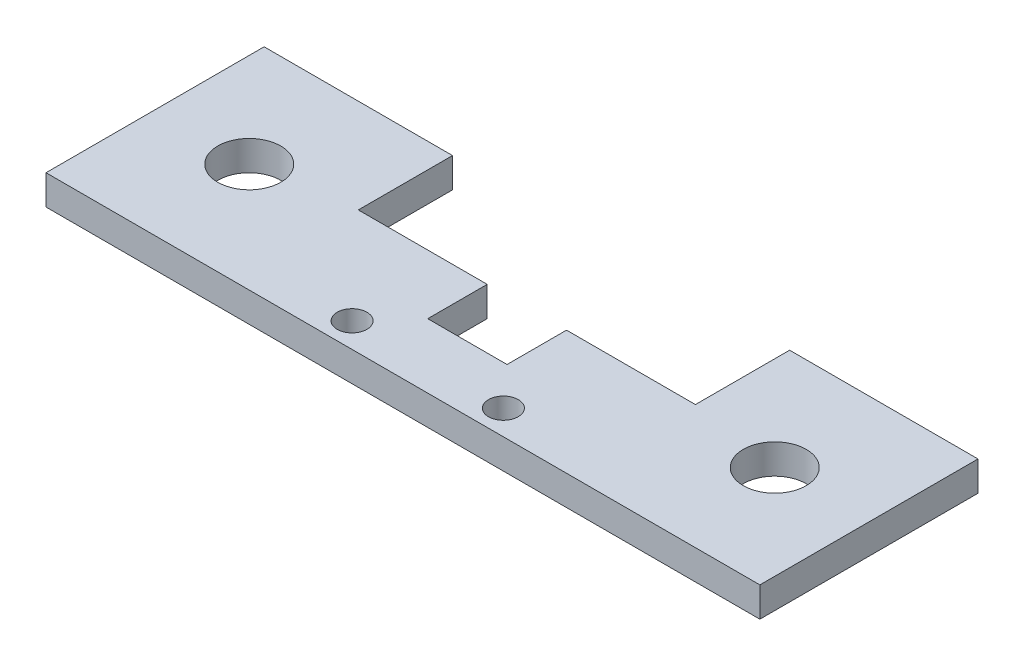
SolidWorks part; units mm, degrees
ref_plane "Front Plane" through (0, 0, 0) normal (0, 0, 1) x (1, 0, 0)
ref_plane "Top Plane" through (0, 0, 0) normal (0, 1, 0) x (1, 0, 0)
ref_plane "Right Plane" through (0, 0, 0) normal (1, 0, 0) x (0, 0, -1)
sketch "Sketch1" plane through (0, 0, 0) normal (0, 1, 0) x (1, 0, 0)
  line L0 (-4, 0) -> (-4, -5.5) construction
  line L1 (0, 0) -> (-8, 0)
  line L2 (0, 0) -> (0, -6)
  line L3 (0, -6) -> (-8, -6)
  line L4 (-8, 0) -> (-8, -6)
  line L5 (-21, 0) -> (13, 0)
  line L6 (-21, 0) -> (-21, -12.5)
  line L7 (-21, -12.5) -> (13, -12.5)
  line L8 (13, 0) -> (13, -12.5)
  line L9 (13, 9.5) -> (32, 9.5)
  line L10 (-21, -12.5) -> (13, 0) construction
  line L11 (-4, -5.5) -> (-4, -13.3) construction
  line L12 (-14.13, -13.3) -> (6.13, -13.3) construction
  line L13 (6.13, -13.3) -> (6.13, 2.3) construction
  line L14 (6.13, -13.3) -> (3.63, -13.3) construction
  line L15 (3.63, -13.3) -> (3.63, -10) construction
  line L16 (-4, -5.5) -> (6.13, -5.5) construction
  line L17 (-14.13, -13.3) -> (-14.13, 2.3) construction
  line L18 (-14.13, 2.3) -> (6.13, 2.3) construction
  line L19 (-4, -9.35) -> (-4, -17.6) construction
  line L20 (-21, -12.5) -> (-40, -12.5)
  line L21 (-21, -12.5) -> (-21, 9.5)
  line L22 (-21, 9.5) -> (-40, 9.5)
  line L23 (-40, -12.5) -> (-40, 9.5)
  line L24 (13, 0) -> (13, -12.5)
  line L25 (13, -12.5) -> (32, -12.5)
  line L26 (32, -12.5) -> (32, 9.5)
  line L27 (-30.5, -12.5) -> (-30.5, 9.5) construction
  line L28 (-40, -1.5) -> (-21, -1.5) construction
  line L29 (32, -1.5) -> (13, -1.5) construction
  line L30 (22.5, -12.5) -> (22.5, 9.5) construction
  line L31 (13, 0) -> (13, 9.5)
  circle A0 centre (3.63, -10) radius 1.5
  circle A1 centre (-11.63, -10) radius 1.5
  circle A2 centre (-30.5, -1.5) radius 3.175
  circle A3 centre (22.5, -1.5) radius 3.175
  point P28 (-14.13, -5.5)
  dimension "D10" = 3
  dimension "D4" = 6.35
  dimension "D1" = 8
  dimension "D2" = 6
  dimension "D3" = 34
  dimension "D5" = 5.5
  dimension "D6" = 7.8
  dimension "D7" = 10.13
  dimension "D8" = 2.5
  dimension "D9" = 2.5
  dimension "D11" = 12.5
  dimension "D12" = 19
  dimension "D13" = 22
  dimension "D14" = 19
  dimension "D15" = 11
extrude "Boss-Extrude1" add sketch "Sketch1" along normal blind 3 contours L8 L5 L2 L3 L4 L6 L7 A0 A1 | L23 L20 L6 L21 L22 A2 | L31 L8 L25 L26 L9 A3 region at (-4, 0, 6.5338) region at (13.2907, 0, -4.75) region at (-21.2907, 0, 6.25)
